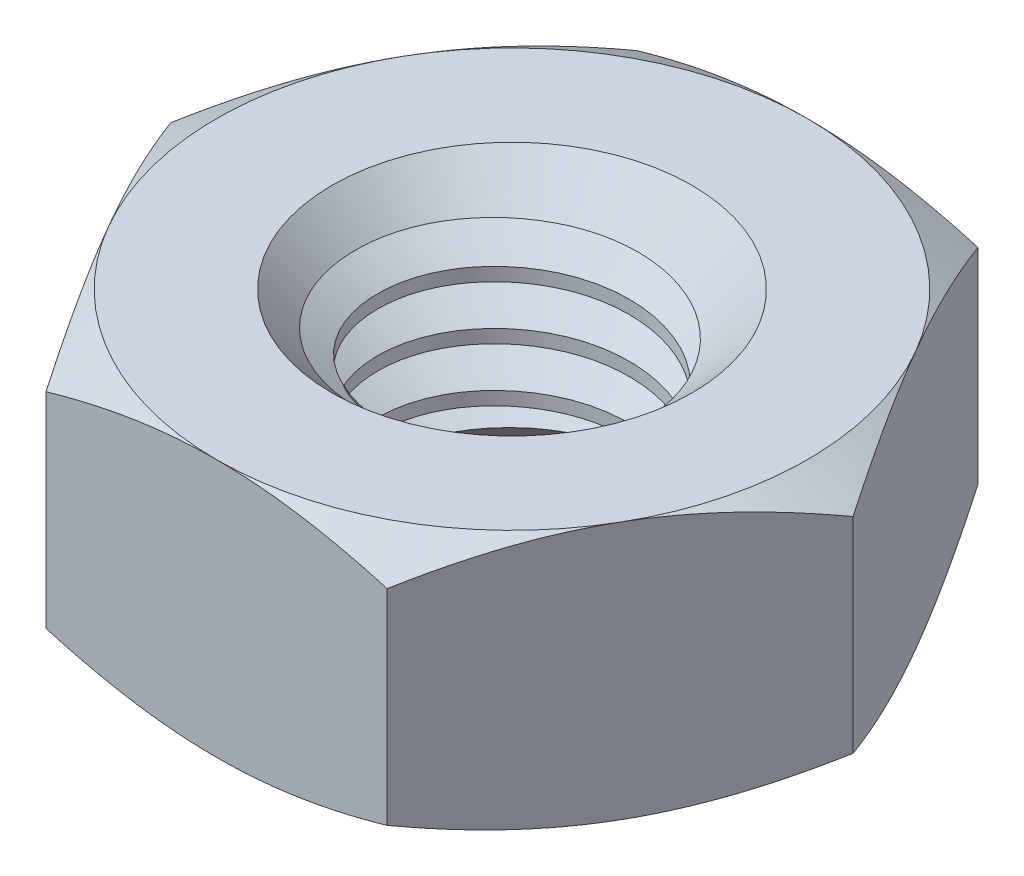
SolidWorks part; units mm, degrees
ref_plane "Front" through (0, 0, 0) normal (0, 0, 1) x (1, 0, 0)
ref_plane "Top" through (0, 0, 0) normal (0, 1, 0) x (1, 0, 0)
ref_plane "Right" through (0, 0, 0) normal (1, 0, 0) x (0, 0, -1)
sketch "Çizim1" plane through (0, 0, 0) normal (0, 0, 1) x (1, 0, 0)
  line L1 (3.1754, 0) -> (1.5877, 2.75)
  line L2 (1.5877, 2.75) -> (-1.5877, 2.75)
  line L3 (-1.5877, 2.75) -> (-3.1754, 0)
  line L4 (-3.1754, 0) -> (-1.5877, -2.75)
  line L5 (-1.5877, -2.75) -> (1.5877, -2.75)
  line L6 (1.5877, -2.75) -> (3.1754, 0)
  circle A0 centre (0, 0) radius 2.75 construction
  dimension "D1" = 5.5
extrude "Yükseklik-Ekstrüzyon1" add sketch "Çizim1" along normal blind 2.4
sketch "Çizim2" plane through (0, 0, 2.4) normal (0, 0, 1) x (1, 0, 0)
  circle A0 centre (0, 0) radius 2.75
extrude "Kes-Ekstrüzyon1" cut sketch "Çizim2" against normal blind 2.4 draft 60 flip side to cut
sketch "Çizim3" plane through (0, 0, 0) normal (0, 0, -1) x (-1, 0, 0)
  circle A0 centre (0, 0) radius 2.75
extrude "Kes-Ekstrüzyon2" cut sketch "Çizim3" against normal blind 2.4 draft 60 flip side to cut
sketch "Çizim4" plane through (0, 0, 0) normal (0, 0, -1) x (-1, 0, 0)
  circle A0 centre (0, 0) radius 1.175
  dimension "D1" = 2.35
extrude "Kes-Ekstrüzyon3" cut sketch "Çizim4" against normal blind 2.4
chamfer "Pah1" distance 0.5 angle 45 2 edges at (-1.175, 0, 2.4) (-1.175, 0, 0)
sketch "Çizim5" plane through (0, 0, 2.4) normal (0, 0, 1) x (1, 0, 0)
  circle A0 centre (0, 0) radius 1.175
curve "Helis/Spiral1" pitch 0.5 height 3 radius 1.175 centre (0, 0, 2.4) axis (0, 0, -1) start towards (-1, 0, 0)
ref_plane "Düzlem1" through (-1.175, 0, -0.6) normal (0, 0.9977, -0.0676) x (1, 0, 0)
sketch "Çizim6" plane through (-1.175, 0, -0.6) normal (0, 0.9977, -0.0676) x (1, 0, 0)
  line L1 (-0.325, 0) -> (0.0987, -0.2446)
  line L3 (0.0987, 0.2446) -> (-0.325, 0)
  line L4 (0.0987, 0.2446) -> (0.0987, -0.2446)
  line L5 (0.1625, 0) -> (0.1625, 0.2815) [skipped]
  circle A0 centre (0, 0) radius 0.1625 construction
  dimension "D1" = 0.325
sweep "Kes-Süpür1" cut profiles "Çizim6" path "Helis/Spiral1" align with end faces yes
move or copy body "Body-Move/Copy1" bodies to move or copy 105 copy no rotation origin (0, 0, 1.1993) rotation axis (1, 0, 0) rotation angle 90
sketch "Sketch1" plane through (0, -1.2007, 0) normal (0, -1, 0) x (1, 0, 0)
  point P0 (0, 1.1993)
